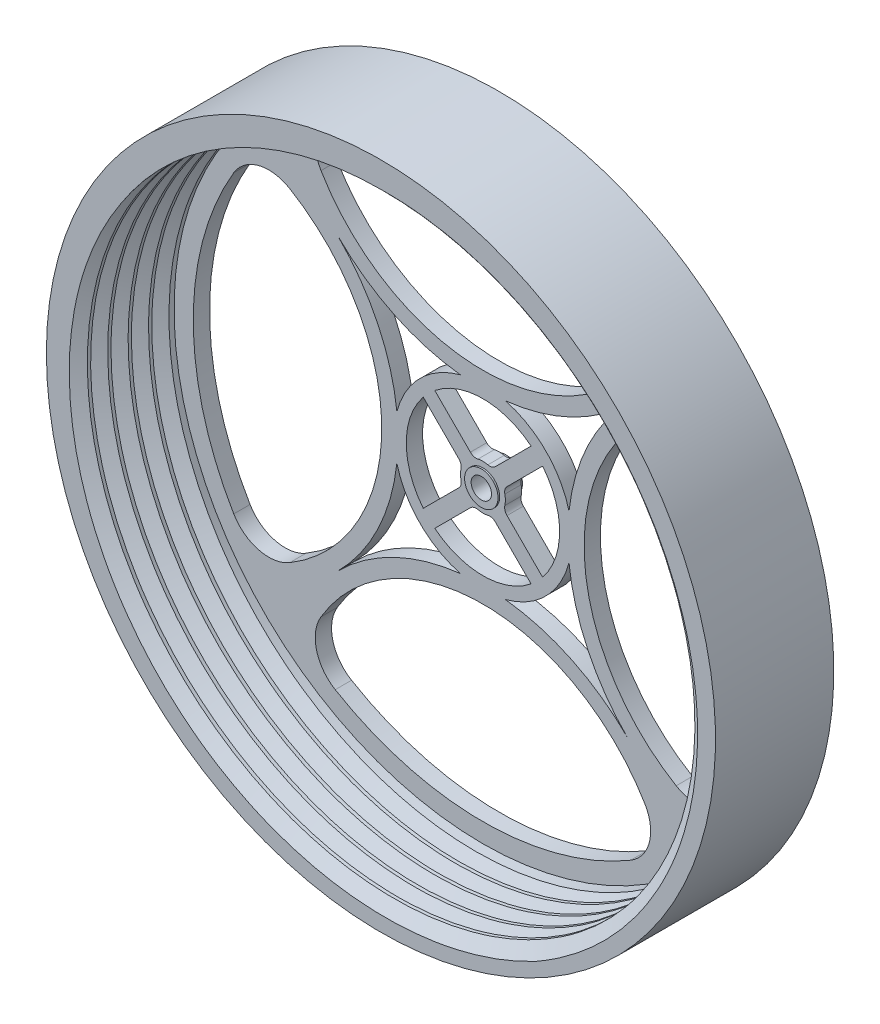
SolidWorks part; units mm, degrees
ref_plane "Front Plane" through (0, 0, 0) normal (0, 0, 1) x (1, 0, 0)
ref_plane "Top Plane" through (0, 0, 0) normal (0, 1, 0) x (1, 0, 0)
ref_plane "Right Plane" through (0, 0, 0) normal (1, 0, 0) x (0, 0, -1)
sketch "Sketch22" plane through (0, 0, 0) normal (0, 0, -1) x (-1, 0, 0)
  circle A0 centre (0, 0) radius 39.5 construction
  circle A1 centre (0, 0) radius 41
  circle A2 centre (0, 0) radius 36 construction
  circle A4 centre (0, 0) radius 37.85
  dimension "D1" = 1.5
  dimension "D2" = 79
  dimension "D3" = 82
  dimension "D4" = 72
  dimension "D5" = 1.85
  dimension "D6" = 1.65
  dimension "D7" = 5
extrude "Boss-Extrude6" add sketch "Sketch22" along normal blind 12.5
sketch "Sketch23" plane through (0, 0, -12.5) normal (0, 0, -1) x (-1, 0, 0)
  line L0 (0, 0) -> (-67.0997, 0) construction
  line L1 (0, 0) -> (-47.116, 47.116) construction
  line L2 (0, -45.2124) -> (0, 0) construction
  line L3 (0, 0) -> (-18.9505, -18.9505) construction
  line L4 (-37.451, 40.2795) -> (56.9896, -54.1612) construction
  line L5 (-40.2795, 37.451) -> (54.1612, -56.9896) construction
  line L6 (-40.2795, 37.451) -> (-37.451, 40.2795) construction
  line L7 (-7.3146, 5.9003) -> (-2.9502, 1.5359)
  line L8 (56.9896, -54.1612) -> (54.1612, -56.9896) construction
  line L9 (-5.9003, 7.3146) -> (-1.5359, 2.9502)
  line L10 (-2.9502, -1.5359) -> (-7.3146, -5.9003)
  line L11 (1.5359, 2.9502) -> (5.9003, 7.3146)
  line L12 (-1.5359, -2.9502) -> (-5.9003, -7.3146)
  line L13 (2.9502, 1.5359) -> (7.3146, 5.9003)
  line L14 (1.5359, -2.9502) -> (5.9003, -7.3146)
  line L16 (7.3146, -5.9003) -> (2.9502, -1.5359)
  circle A0 centre (0, 0) radius 41
  arc A1 (-18.1023, -30.5378) -> (18.1023, -30.5378) centre (0, 0) ccw
  circle A2 centre (0, 0) radius 41 construction
  arc A3 (-30.5378, 18.1023) -> (-30.5378, -18.1023) centre (0, 0) ccw
  arc A4 (-23.6781, -19.8484) -> (-23.6781, 19.8484) centre (-35.5, 0) ccw
  arc A5 (30.5378, -18.1023) -> (30.5378, 18.1023) centre (0, 0) ccw
  arc A6 (23.6781, 19.8484) -> (23.6781, -19.8484) centre (35.5, 0) ccw
  arc A7 (-7.3146, 5.9003) -> (5.9003, -7.3146) centre (0, 0) ccw
  circle A8 centre (0, 0) radius 1.25
  arc A9 (-2.682, 0.6078) -> (-2.682, -0.6078) centre (0, 0) ccw
  arc A10 (19.8484, -23.6781) -> (-19.8484, -23.6781) centre (0, -35.5) ccw
  arc A11 (18.1023, 30.5378) -> (-18.1023, 30.5378) centre (0, 0) ccw
  arc A12 (-19.8484, 23.6781) -> (19.8484, 23.6781) centre (0, 35.5) ccw
  arc A13 (0.6078, 2.682) -> (-0.6078, 2.682) centre (0, 0) ccw
  arc A14 (2.682, -0.6078) -> (2.682, 0.6078) centre (0, 0) ccw
  arc A15 (-0.6078, -2.682) -> (0.6078, -2.682) centre (0, 0) ccw
  arc A16 (-1.5359, 2.9502) -> (-0.6078, 2.682) centre (-0.8288, 3.6573) ccw
  arc A17 (1.5359, 2.9502) -> (0.6078, 2.682) centre (0.8288, 3.6573) cw
  arc A18 (2.9502, 1.5359) -> (2.682, 0.6078) centre (3.6573, 0.8288) ccw
  arc A19 (2.9502, -1.5359) -> (2.682, -0.6078) centre (3.6573, -0.8288) cw
  arc A20 (1.5359, -2.9502) -> (0.6078, -2.682) centre (0.8288, -3.6573) ccw
  arc A21 (-0.6078, -2.682) -> (-1.5359, -2.9502) centre (-0.8288, -3.6573) ccw
  arc A22 (-2.9502, 1.5359) -> (-2.682, 0.6078) centre (-3.6573, 0.8288) cw
  arc A23 (-2.9502, -1.5359) -> (-2.682, -0.6078) centre (-3.6573, -0.8288) ccw
  arc A24 (5.9003, 7.3146) -> (-5.9003, 7.3146) centre (0, 0) ccw
  arc A25 (7.3146, -5.9003) -> (7.3146, 5.9003) centre (0, 0) ccw
  arc A26 (-23.6781, 19.8484) -> (-30.5378, 18.1023) centre (-26.2367, 15.5526) ccw
  arc A27 (-19.8484, 23.6781) -> (-18.1023, 30.5378) centre (-15.5526, 26.2367) cw
  arc A28 (18.1023, 30.5378) -> (19.8484, 23.6781) centre (15.5526, 26.2367) cw
  arc A29 (23.6781, 19.8484) -> (30.5378, 18.1023) centre (26.2367, 15.5526) cw
  arc A30 (23.6781, -19.8484) -> (30.5378, -18.1023) centre (26.2367, -15.5526) ccw
  arc A31 (19.8484, -23.6781) -> (18.1023, -30.5378) centre (15.5526, -26.2367) cw
  arc A32 (-18.1023, -30.5378) -> (-19.8484, -23.6781) centre (-15.5526, -26.2367) cw
  arc A33 (-23.6781, -19.8484) -> (-30.5378, -18.1023) centre (-26.2367, -15.5526) cw
  arc A34 (2.7398, -10.5477) -> (10.5477, -2.7398) centre (0, 0) ccw
  arc A35 (-17.75, -17.75) -> (-2.7398, -10.5477) centre (0, -35.5) cw
  arc A36 (-17.75, -17.75) -> (-10.5477, -2.7398) centre (-35.5, 0) ccw
  arc A37 (-17.75, 17.75) -> (-10.5477, 2.7398) centre (-35.5, 0) cw
  arc A38 (-17.75, 17.75) -> (-2.7398, 10.5477) centre (0, 35.5) ccw
  arc A39 (17.75, 17.75) -> (2.7398, 10.5477) centre (0, 35.5) cw
  arc A40 (10.5477, 2.7398) -> (17.75, 17.75) centre (35.5, 0) cw
  arc A41 (10.5477, -2.7398) -> (17.75, -17.75) centre (35.5, 0) ccw
  arc A42 (17.75, -17.75) -> (2.7398, -10.5477) centre (0, -35.5) ccw
  arc A43 (10.5477, 2.7398) -> (2.7398, 10.5477) centre (0, 0) ccw
  arc A44 (-2.7398, 10.5477) -> (-10.5477, 2.7398) centre (0, 0) ccw
  arc A45 (-10.5477, -2.7398) -> (-2.7398, -10.5477) centre (0, 0) ccw
  point P20 (55.5754, -55.5754)
  point P21 (-38.8653, 38.8653)
  point P30 (0, 9.3977)
  point P31 (0, 12.3977)
  point P55 (1.1043, 2.5185)
  point P60 (2.5185, -1.1043)
  point P65 (-1.1043, -2.5185)
  point P71 (-27.9829, 21.8451)
  point P78 (27.9829, 21.8451)
  point P81 (27.9829, -21.8451)
  point P88 (-12.3977, 0)
  point P92 (-9.3977, 0)
  dimension "D1" = 5.5
  dimension "D2" = 4
  dimension "D7" = 1
  dimension "D3" = 2.5
  dimension "D4" = 1.5
  dimension "D8" = 5
  dimension "D9" = 3
  dimension "D10" = 1.5
  dimension "D5" = 3
  dimension "D6" = 1
extrude "Boss-Extrude7" add sketch "Sketch23" along normal blind 2
sketch "Sketch24" plane through (0, 0, -12.5) normal (0, 0, 1) x (1, 0, 0)
  circle A0 centre (0, 0) radius 1.25
  circle A1 centre (0, 0) radius 2.05
  dimension "D1" = 4.1
  dimension "D2" = 2.5
extrude "Boss-Extrude8" add sketch "Sketch24" along normal blind 0.2 and the other way blind 2.8
sketch "Sketch26" plane through (0, 0, 0) normal (0, 0, 1) x (1, 0, 0)
  circle A0 centre (0, 0) radius 41
  circle A1 centre (0, 0) radius 41 construction
curve "Helix/Spiral1" pitch 2.5 height 12.5 turns 5
sketch "Sketch27" plane through (0, 0, 0) normal (1, 0, 0) x (0, 0, -1)
  line L0 (-1.05, 39.45) -> (-2.1, 37.85)
  line L1 (-2.1, 37.85) -> (-2.1, 36.85)
  line L2 (-2.1, 36.85) -> (0, 36.85)
  line L3 (0, 36.85) -> (0, 37.85)
  line L4 (0, 37.85) -> (-1.05, 39.45)
  line L5 (-2.1, 37.85) -> (0, 37.85) construction
  point P3 (0, 37.85)
  dimension "D1" = 1
  dimension "D2" = 2.1
  dimension "D3" = 2.6
sweep "Cut-Sweep1" cut profiles "Sketch27" path "Helix/Spiral1"
